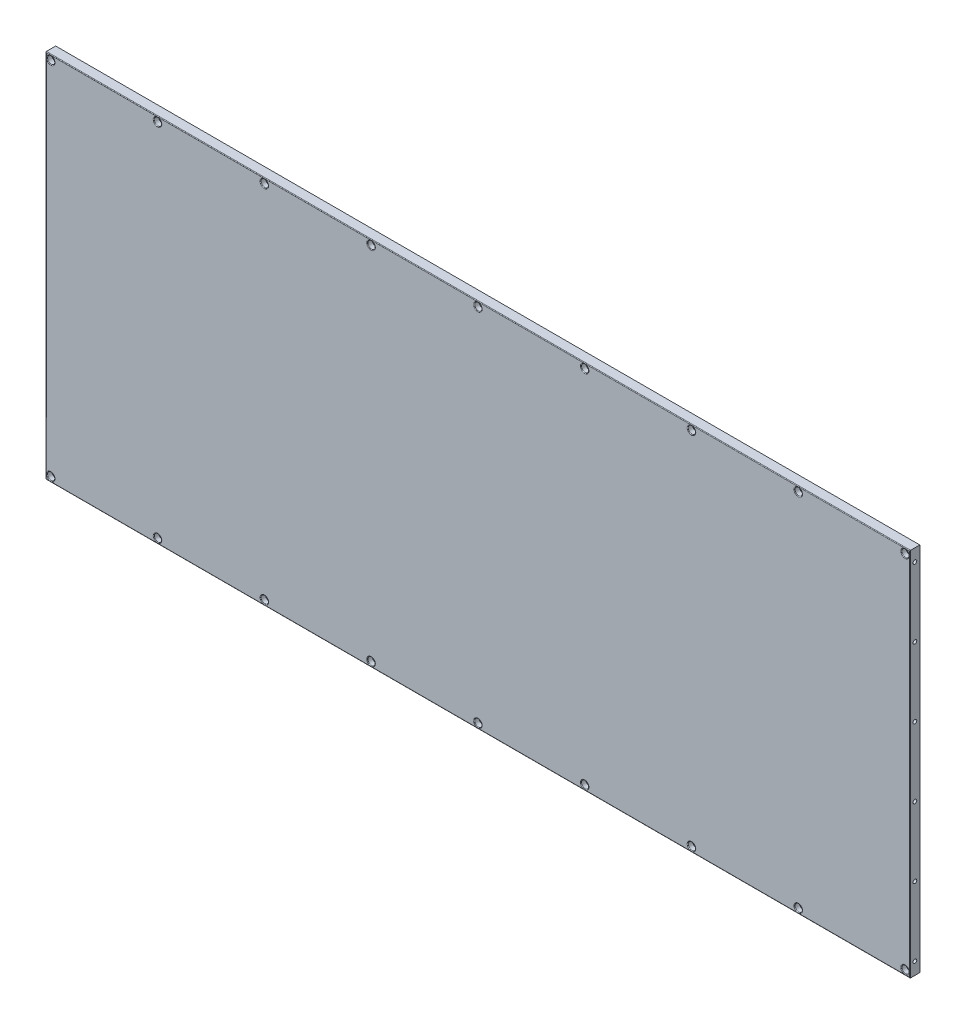
SolidWorks part; units mm, degrees
ref_plane "Front Plane" through (0, 0, 0) normal (0, 0, 1) x (1, 0, 0)
ref_plane "Top Plane" through (0, 0, 0) normal (0, 1, 0) x (1, 0, 0)
ref_plane "Right Plane" through (0, 0, 0) normal (1, 0, 0) x (0, 0, -1)
sketch "Sketch1" plane through (0, 0, 0) normal (0, 0, 1) x (1, 0, 0)
  line L1 (0, 0) -> (700, 0)
  line L2 (0, 0) -> (0, 300)
  line L3 (0, 300) -> (700, 300)
  line L4 (700, 0) -> (700, 300)
extrude "Boss-Extrude1" add sketch "Sketch1" along normal blind 8
sketch "Sketch4" plane through (0, 0, 8) normal (0, 0, 1) x (1, 0, 0)
  line L0 (700, 300) -> (0, 300) construction
  line L1 (0, 300) -> (0, 0) construction
  circle A0 centre (4, 296) radius 3
  dimension "D1" = 4
  dimension "D2" = 4
extrude "Cut-Extrude2" cut sketch "Sketch4" against normal blind 4
pattern_linear "LPattern1" count 9 spacing 86.5 along (1, 0, 0) count 2 spacing 292 along (0, -1, 0) of "Cut-Extrude2"
sketch "Sketch7" plane through (0, 0, 4) normal (1, 0, 0) x (0, 0, -1)
  line L0 (-4, 300) -> (4, 300) construction
  circle A0 centre (0, 290) radius 1.5
  point P4 (0, 300)
  dimension "D1" = 10
extrude "Cut-Extrude7" cut sketch "Sketch7" along normal blind 20
fillet "Fillet1" radius 0.5 22 edges at (353, 4, 8) (266.5, 4, 8) (180, 4, 8) (93.5, 4, 8) (7, 4, 8) (353, 296, 8) (266.5, 296, 8) (180, 296, 8) (350, 300, 8) (700, 150, 8) (350, 0, 8) (0, 150, 8) (7, 296, 8) (93.5, 296, 8) (699, 4, 8) (612.5, 4, 8) (526, 4, 8) (439.5, 4, 8) (699, 296, 8) (612.5, 296, 8) (526, 296, 8) (439.5, 296, 8)
pattern_linear "LPattern2" count 6 spacing 56 along (0, -1, 0) of "Cut-Extrude7"
ref_plane "Plane1" through (350, 0, 0) normal (1, 0, 0) x (0, 0, -1)
mirror "Mirror1" about plane through (350, 0, 0) normal (1, 0, 0) of "Cut-Extrude7", "LPattern2"
